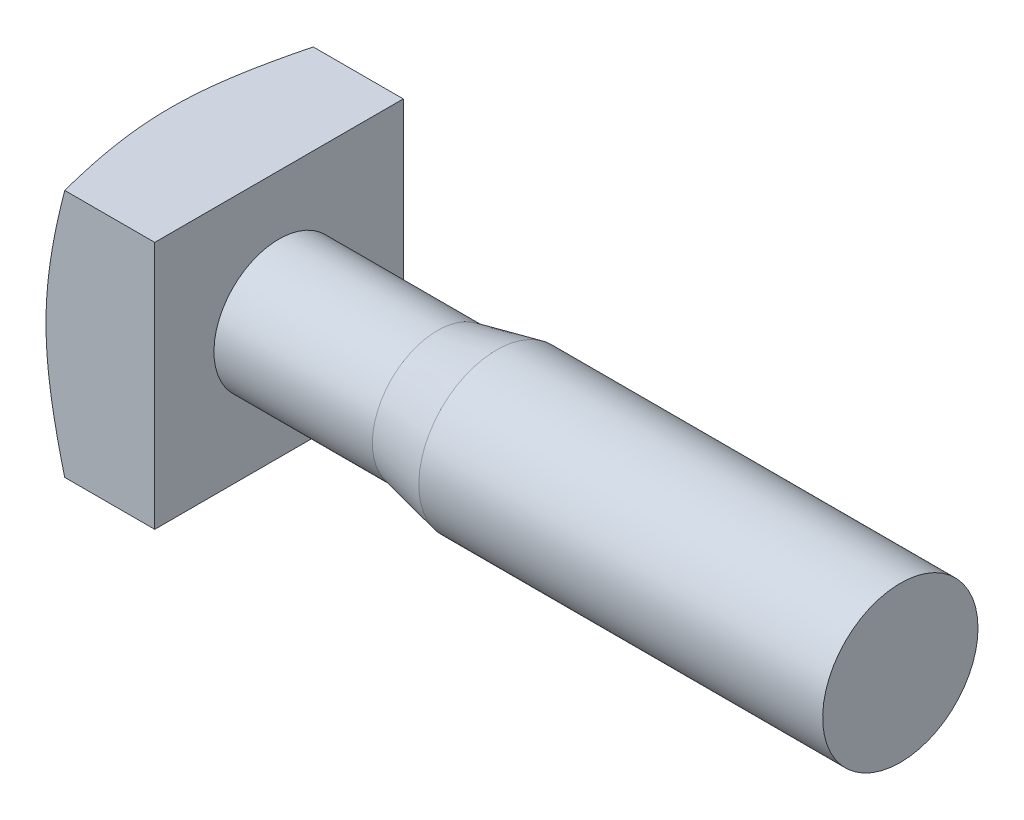
SolidWorks part; units mm, degrees
ref_plane "Front" through (0, 0, 0) normal (0, 0, 1) x (1, 0, 0)
ref_plane "Top" through (0, 0, 0) normal (0, 1, 0) x (1, 0, 0)
ref_plane "Right" through (0, 0, 0) normal (1, 0, 0) x (0, 0, -1)
sketch "Sketch1" plane through (0, 0, 0) normal (1, 0, 0) x (0, 0, -1)
  line L0 (0, 36.5746) -> (0, -34.3123) construction
  line L1 (-37.5173, 0) -> (33.3696, 0) construction
  line L3 (-8, 8) -> (8, 8)
  line L4 (-8, 8) -> (-8, -8)
  line L5 (-8, -8) -> (8, -8)
  line L6 (8, 8) -> (8, -8)
extrude "BaseHead" add sketch "Sketch1" along normal blind 7
ref_plane "Plane1" through (0, 0, 0) normal (0, -0.7071, -0.7071) x (1, 0, 0)
sketch "Sketch4" plane through (-7.1814, -8, 8) normal (0, -0.7071, -0.7071) x (-1, 0, 0)
  line L0 (-16.1283, 11.3137) -> (-5.416, 11.3137) construction
  line L1 (-7.1814, 19.3137) -> (-7.1814, 22.6274)
  line L2 (-7.1814, 22.6274) -> (-8.3875, 22.6274)
  line L3 (-8.3875, 22.6274) -> (-7.1814, 19.3137)
  dimension "D1" = 20
  dimension "D2" = 16
revolve "HeadChamfer" cut sketch "Sketch4" angle 360 about L0
sketch "Sketch2" plane through (7, 0, 0) normal (1, 0, 0) x (0, 0, -1)
  circle A0 centre (0, 0) radius 5
extrude "BaseBody" add sketch "Sketch2" along normal blind 40
cosmetic thread "ThreadCosmetic1" [suppressed] parameters "D2"=8.376
sketch "Sketch5" plane through (-43.2091, 5, 0) normal (0, 0, 1) x (-1, 0, 0)
  line L0 (-39.4181, 5) -> (-75.6573, 5) construction
  line L1 (-64.2091, 10) -> (-50.2091, 10)
  line L2 (-50.2091, 13) -> (-50.2091, -3) construction
  line L4 (-64.2091, 10) -> (-60.4091, 9.188)
  line L5 (-60.4091, 9.188) -> (-50.2091, 9.188)
  line L6 (-90.2091, 10) -> (-90.2091, 0) construction
  line L7 (-50.2091, 10) -> (-50.2091, 9.188)
  line L8 (-50.2091, 10) -> (-90.2091, 10) construction
  dimension "b" = 26
  dimension "dz" = 8.376
  dimension "x" = 3.8
revolve "Cut-Revolve1" cut sketch "Sketch5" angle 360 about L0
sketch "Sketch6" plane through (0, 0, 0) normal (0, 0, 1) x (1, 0, 0)
  line L0 (46.594, 5.812) -> (47.406, 5.812)
  line L1 (47.406, 5.812) -> (47.406, 5)
  line L2 (47.406, 5) -> (47, 4.2968)
  line L3 (47, 4.2968) -> (46.594, 5)
  line L4 (46.594, 5) -> (46.594, 5.812)
  line L5 (47, -5) -> (47, 5) construction
  line L8 (0, 0) -> (57.2897, 0) construction
  line L9 (8.9468, 0) -> (-1.7654, 0) construction
  dimension "D1" = 0.812
  dimension "D2" = 10
revolve "Cut-Revolve10" [suppressed] cut sketch "Sketch6" angle 360
pattern_linear "LPattern10" [suppressed] count 41 of bodies 107
equation "\"D2@Sketch4\" = \"s@Sketch1\""
equation "\"D1@Sketch6\" =  ( \"d@Sketch2\" - \"D2@ThreadCosmetic1\" )  / 2"
equation "\"pitch@LPattern10\" = 1.2 * \"D1@Sketch6\""
equation "\"D1@LPattern10\" =  \"l@BaseBody\"  / \"pitch@LPattern10\""
equation "\"D2@Sketch6\" = \"d@Sketch2\""
